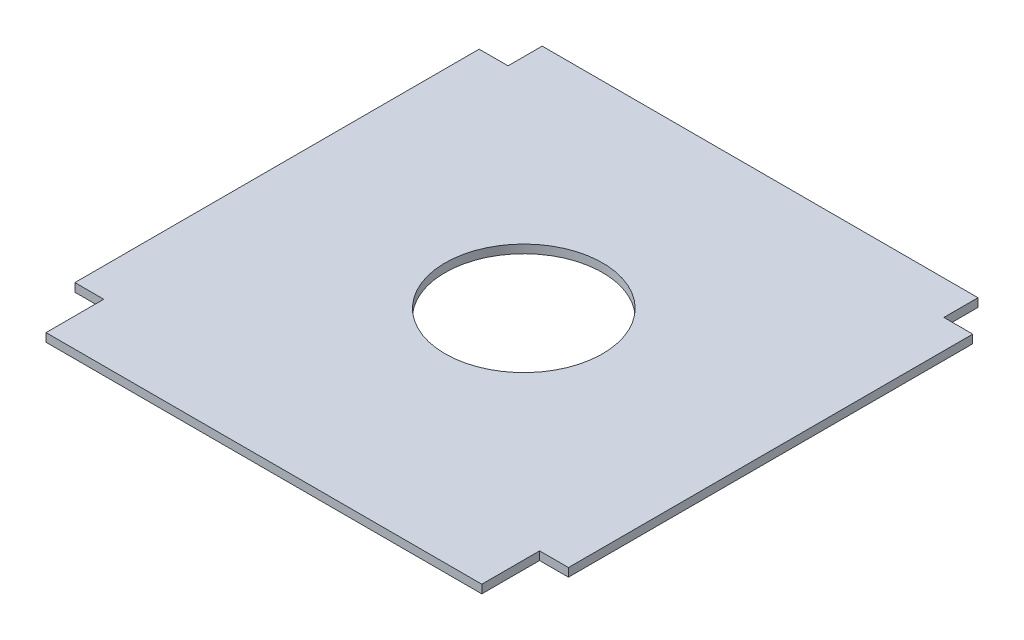
SolidWorks part; units mm, degrees
ref_plane "Front Plane" through (0, 0, 0) normal (0, 0, 1) x (1, 0, 0)
ref_plane "Top Plane" through (0, 0, 0) normal (0, 1, 0) x (1, 0, 0)
ref_plane "Right Plane" through (0, 0, 0) normal (1, 0, 0) x (0, 0, -1)
sketch "Sketch1" plane through (0, 0, 0) normal (0, 1, 0) x (1, 0, 0)
  line L5 (-41.5, -38.5) -> (41.5, 38.5) construction
  line L6 (-41.5, 38.5) -> (41.5, -38.5) construction
  line L8 (-41.5, 38.5) -> (-41.5, 45)
  line L9 (-41.5, 45) -> (41.5, 45)
  line L10 (41.5, 38.5) -> (41.5, 45)
  line L12 (-41.5, -38.5) -> (-41.5, -49.5)
  line L13 (-41.5, -49.5) -> (41.5, -49.5)
  line L14 (41.5, -38.5) -> (41.5, -49.5)
  line L15 (-41.5, 38.5) -> (-47, 38.5)
  line L17 (-41.5, -38.5) -> (-47, -38.5)
  line L18 (-47, 38.5) -> (-47, -38.5)
  line L19 (41.5, 38.5) -> (47, 38.5)
  line L21 (41.5, -38.5) -> (47, -38.5)
  line L22 (47, 38.5) -> (47, -38.5)
  point P0 (0, 0)
  dimension "D1" = 83
  dimension "D2" = 77
  dimension "D3" = 5.5
  dimension "D4" = 11
  dimension "D5" = 6.5
  dimension "D6" = 5.5
extrude "Boss-Extrude1" add sketch "Sketch1" along normal blind 1.6
sketch "Sketch2" plane through (0, 1.6, 0) normal (0, 1, 0) x (1, 0, 0)
  circle A0 centre (0, 0) radius 15
  dimension "D1" = 30
extrude "Cut-Extrude1" cut sketch "Sketch2" against normal blind 1.6
